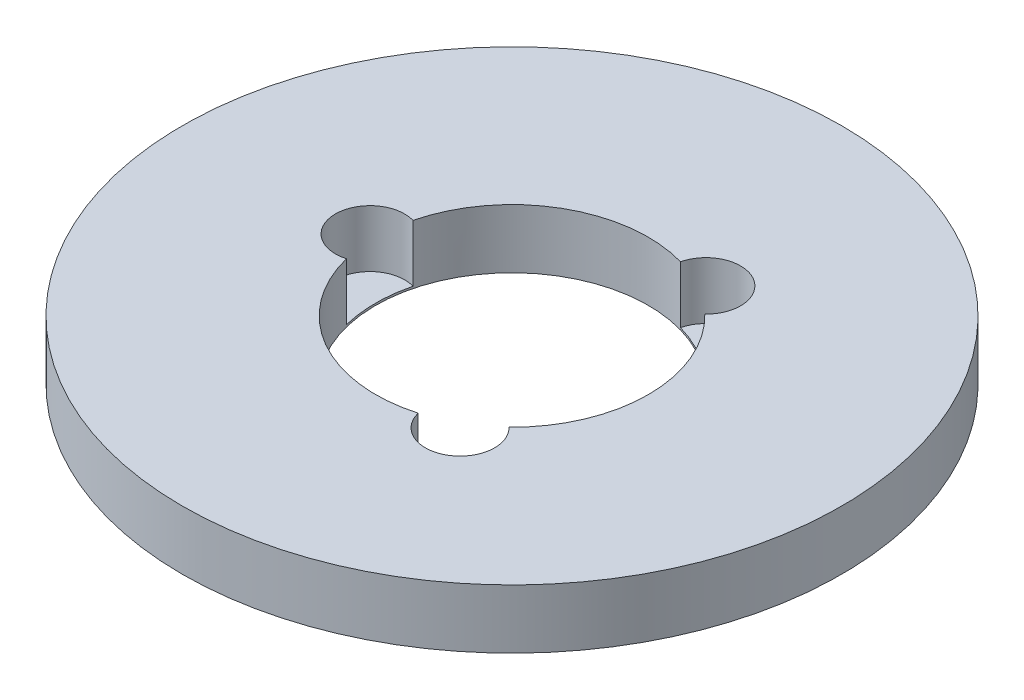
SolidWorks part; units mm, degrees
ref_plane "Front Plane" through (0, 0, 0) normal (0, 0, 1) x (1, 0, 0)
ref_plane "Top Plane" through (0, 0, 0) normal (0, 1, 0) x (1, 0, 0)
ref_plane "Right Plane" through (0, 0, 0) normal (1, 0, 0) x (0, 0, -1)
sketch "Sketch1" plane through (0, 0, 0) normal (0, 1, 0) x (1, 0, 0)
  circle A0 centre (0, 0) radius 72.5
  dimension "FLANGE_OD" = 145
extrude "Boss-Extrude1" add sketch "Sketch1" along normal blind 13
sketch "Sketch2" plane through (0, 0, 0) normal (0, 1, 0) x (1, 0, 0)
  circle A0 centre (0, 0) radius 30
  dimension "BORE_D" = 60
extrude "Cut-Extrude1" cut sketch "Sketch2" along normal through all
sketch "Sketch3" plane through (0, 13, 0) normal (0, 1, 0) x (1, 0, 0)
  circle A0 centre (0, 0) radius 31.2346 construction
  circle A1 centre (-31.2346, 0) radius 7.6188
  dimension "BOLT_D" = 15.2375
  dimension "BOLT_PCD" = 62.4693
extrude "Cut-Extrude2" cut sketch "Sketch3" against normal blind 12.5566
pattern_circular "CirPattern1" count 3 over 360 about axis through (0, 0, 0) along (0, 1, 0) of "Cut-Extrude2"
